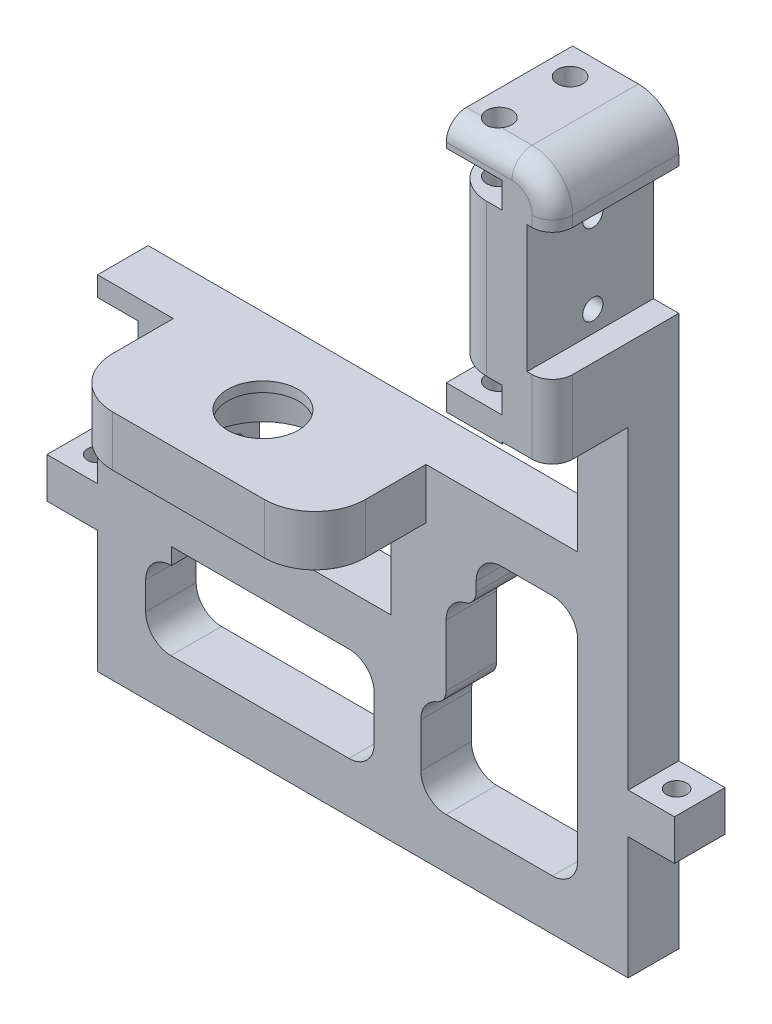
SolidWorks part; units mm, degrees
material "PLA Black"
ref_plane "Front Plane" through (0, 0, 0) normal (0, 0, 1) x (1, 0, 0)
ref_plane "Top Plane" through (0, 0, 0) normal (0, 1, 0) x (1, 0, 0)
ref_plane "Right Plane" through (0, 0, 0) normal (1, 0, 0) x (0, 0, -1)
sketch "Sketch1" plane through (0, 0, 0) normal (0, 0, 1) x (1, 0, 0)
  line L0 (-68.0673, -53.1516) -> (46.9327, -53.1516)
  line L1 (56.0827, -20.9516) -> (56.0827, -28.9516)
  line L2 (56.0827, -20.9516) -> (46.9327, -20.9516)
  line L3 (46.9327, -20.9516) -> (46.9327, 91.0484)
  line L4 (46.9327, 91.0484) -> (36.6057, 91.0484)
  line L5 (36.9327, 86.0484) -> (36.9327, 80.9484)
  line L6 (36.9327, 25.6935) -> (36.9327, 22.1505)
  line L7 (36.9327, 22.1505) -> (36.9327, 14.8484)
  line L8 (36.9327, 14.8484) -> (-58.0673, 14.8484)
  line L9 (-58.0673, 14.8484) -> (-58.0673, -20.9516)
  line L10 (-58.0673, -20.9516) -> (-68.0673, -20.9516)
  line L11 (-68.0673, -20.9516) -> (-68.0673, -53.1516)
  line L12 (56.0827, -28.9516) -> (46.9327, -28.9516)
  line L13 (46.9327, -28.9516) -> (46.9327, -53.1516)
  line L14 (36.9327, 50.9484) -> (36.9327, 45.8484)
  line L15 (36.6057, 91.0484) -> (25.9327, 91.0484)
  line L16 (36.9327, 80.9484) -> (25.9327, 80.9484)
  line L17 (36.9327, 86.0484) -> (25.9327, 86.0484)
  line L18 (25.9327, 91.0484) -> (25.9327, 86.0484)
  line L19 (36.9327, 40.8484) -> (36.9327, 25.6935)
  line L20 (36.9327, 50.9484) -> (25.9327, 50.9484)
  line L21 (25.9327, 80.9484) -> (25.9327, 50.9484)
  line L22 (36.9327, 45.8484) -> (25.9327, 45.8484)
  line L24 (36.9327, 40.8484) -> (25.9327, 40.8484)
  line L25 (25.9327, 45.8484) -> (25.9327, 40.8484)
  dimension "D1" = 30
  dimension "D2" = 5.1
  dimension "D3" = 5.1
  dimension "D4" = 11
  dimension "D5" = 21
  dimension "D6" = 115
  dimension "D7" = 10
  dimension "D8" = 8
  dimension "D9" = 24.2
  dimension "D10" = 26
  dimension "D11" = 5
  dimension "D12" = 5
  dimension "D13" = 112
extrude "Extrude1" add sketch "Sketch1" along normal blind 10
sketch "Sketch2" plane through (0, 0, 10) normal (0, 0, 1) x (1, 0, 0)
  line L0 (25.9327, 91.0484) -> (46.9327, 91.0484)
  line L1 (46.9327, 91.0484) -> (46.9327, 41.2275)
  line L2 (46.9327, -20.9516) -> (46.9327, 91.0484) construction
  line L3 (46.9327, 41.2275) -> (36.9327, 41.2275)
  line L4 (36.9327, 86.0484) -> (36.9327, 80.9484) construction
  line L5 (36.9327, 41.2275) -> (36.9327, 40.8484)
  line L6 (36.9327, 86.0484) -> (25.9327, 86.0484)
  line L7 (25.9327, 86.0484) -> (25.9327, 91.0484)
  line L8 (36.9327, 80.9484) -> (36.9327, 86.0484)
  line L9 (25.9327, 80.9484) -> (36.9327, 80.9484)
  line L10 (25.9327, 80.9484) -> (25.9327, 50.9484)
  line L11 (25.9327, 50.9484) -> (36.9327, 50.9484)
  line L12 (36.9327, 45.8484) -> (36.9327, 50.9484)
  line L13 (25.9327, 45.8484) -> (36.9327, 45.8484)
  line L14 (25.9327, 45.8484) -> (25.9327, 40.8484)
  line L15 (25.9327, 40.8484) -> (36.9327, 40.8484)
extrude "Extrude2" add sketch "Sketch2" along normal blind 15
fillet "Fillet1" radius 8 2 edges at (25.9327, 65.9484, 0) (25.9327, 65.9484, 25)
sketch "Sketch3" plane through (0, 91.0484, 0) normal (0, 1, 0) x (-1, 0, 0)
  line L0 (-46.9327, 0) -> (-25.9327, 0) construction
  line L1 (-30.9327, 0) -> (-30.9327, 25) construction
  line L2 (-46.9327, 25) -> (-25.9327, 25) construction
  line L3 (-25.9327, 25) -> (-25.9327, 0) construction
  circle A0 centre (-30.9327, 5.5) radius 2.5
  circle A1 centre (-30.9327, 19.5) radius 2.5
  dimension "D2" = 5
  dimension "D1" = 14
  dimension "D3" = 5.5
  dimension "D4" = 5
extrude "Cut-Extrude1" cut sketch "Sketch3" against normal blind 53.683
fillet "Fillet4" radius 8 1 edges at (46.9327, 91.0484, 12.5)
fillet "Fillet7" radius 4 3 edges at (46.9327, 62.1379, 25) (32.4327, 91.0484, 25) (44.5895, 88.7052, 25)
sketch "Sketch4" plane through (0, 0, 0) normal (0, 0, -1) x (-1, 0, 0)
  line L0 (-46.9327, -20.9516) -> (-46.9327, 83.0484) construction
  line L1 (-46.9327, 80.9484) -> (-41.9327, 80.9484)
  line L2 (-46.9327, 80.9484) -> (-46.9327, 55.7484)
  line L3 (-46.9327, 55.7484) -> (-41.9327, 55.7484)
  line L4 (-41.9327, 80.9484) -> (-41.9327, 55.7484)
  line L5 (-36.9327, 80.9484) -> (-33.9327, 80.9484) construction
  dimension "D1" = 5
  dimension "D2" = 25.2
extrude "Extrude3" cut sketch "Sketch4" against normal through all
hole_wizard "Ø4.0 (4) Diameter Hole1" positions "3DSketch1" profile "Sketch5" hole size "Ø4.0" standard "Ansi Metric"
sketch3d "3DSketch1"
  line L0 (41.9327, 55.7484, 12) -> (41.9327, 80.9484, 12) construction
  line L1 (41.9327, 55.7484, 25) -> (41.9327, 55.7484, 0) construction
  line L2 (41.9327, 80.9484, 25) -> (41.9327, 80.9484, 0) construction
  line L5 (41.9327, 55.7484, 0) -> (41.9327, 80.9484, 0) construction
  point P0 (41.9327, 75.9484, 12)
  point P2 (41.9327, 59.9484, 12)
  dimension "D1" = 12
  dimension "D2" = 16
  dimension "D3" = 5
sketch "Sketch5" plane through (41.9327, 75.9484, 12) normal (0, 1, 0) x (0, 0, -1)
  line L0 (0, 0) -> (0, 15)
  line L1 (0, 15) -> (2, 15)
  line L2 (2, 15) -> (2, 0)
  line L5 (2, 0) -> (0, 0)
  line L10 (0, 15) -> (-2, 15) construction
  line L11 (0, -6.35) -> (0, 107.95) construction
  dimension "Hole Dia." = 4
  dimension "Hole Depth" = 15
  dimension "Drill Angle" = 180
sketch "Sketch6" plane through (0, 0, 10) normal (0, 0, 1) x (1, 0, 0)
  line L0 (36.9327, 14.8484) -> (-58.0673, 14.8484) construction
  line L1 (6.9327, 14.8484) -> (-43.0673, 14.8484)
  line L2 (6.9327, 14.8484) -> (6.9327, 4.8484)
  line L3 (6.9327, 4.8484) -> (-43.0673, 4.8484)
  line L4 (-43.0673, 14.8484) -> (-43.0673, 4.8484)
  line L5 (46.9327, -20.9516) -> (46.9327, 41.2275) construction
  dimension "D1" = 10
  dimension "D2" = 50
  dimension "D3" = 40
extrude "Extrude4" add sketch "Sketch6" along normal blind 22
sketch "Sketch7" plane through (0, 0, 10) normal (0, 0, 1) x (1, 0, 0)
  line L0 (-43.0673, 4.8484) -> (6.9327, 4.8484) construction
  line L1 (0, 4.8484) -> (-35.9916, 4.8484)
  line L2 (0, 4.8484) -> (0, -14.4098)
  line L3 (0, -14.4098) -> (-35.9916, -14.4098)
  line L4 (-35.9916, 4.8484) -> (-35.9916, -14.4098)
extrude "Extrude5" cut sketch "Sketch7" against normal blind 65
sketch "Sketch8" plane through (0, 4.8484, 0) normal (0, -1, 0) x (1, 0, 0)
  circle A0 centre (-18.5673, 16.7712) radius 7
  circle A1 centre (-18.5673, 16.7712) radius 8 construction
  dimension "D1" = 14
extrude "Extrude6" cut sketch "Sketch8" against normal blind 65
sketch "Sketch9" plane through (0, 4.8484, 0) normal (0, -1, 0) x (1, 0, 0)
  circle A0 centre (-18.5673, 16.7712) radius 11.25
  dimension "D1" = 22.5
extrude "Extrude7" cut sketch "Sketch9" against normal blind 8
sketch "Sketch10" plane through (0, 0, 10) normal (0, 0, 1) x (1, 0, 0)
  line L2 (-68.0673, -53.1516) -> (46.9327, -53.1516) construction
  line L3 (36.9327, 4.8484) -> (16.849, 4.8484)
  line L4 (36.9327, 4.8484) -> (36.9327, -43.1516)
  line L5 (36.9327, -43.1516) -> (16.849, -43.1516)
  line L6 (16.849, 4.8484) -> (16.849, -4.8134)
  line L7 (16.849, -4.8134) -> (10.8978, -4.8134)
  line L8 (46.9327, -20.9516) -> (46.9327, 41.2275) construction
  line L9 (16.849, -43.1516) -> (10.8978, -43.1516)
  line L10 (10.8978, -4.8134) -> (10.8978, -24.4098)
  line L11 (10.8978, -43.1516) -> (5.8917, -43.1516)
  line L12 (-35.9916, -14.4098) -> (0, -14.4098) construction
  line L13 (10.8978, -24.4098) -> (5.8917, -24.4098)
  line L14 (36.9327, 14.8484) -> (6.9327, 14.8484) construction
  line L15 (-43.4499, -27.6686) -> (-48.5527, -27.6686)
  line L16 (-43.4499, -27.6686) -> (-43.4499, -24.4098)
  line L17 (-45.604, -43.1516) -> (-48.5527, -43.1516)
  line L18 (-48.5527, -27.6686) -> (-48.5527, -43.1516)
  line L19 (5.8917, -24.4098) -> (5.8917, -43.1516)
  line L20 (-3.3285, -24.4098) -> (-3.3285, -43.1516)
  line L21 (-3.3285, -24.4098) -> (-43.4499, -24.4098)
  line L22 (-3.3285, -43.1516) -> (-45.604, -43.1516)
  dimension "D1" = 10
  dimension "D2" = 10
  dimension "D3" = 10
  dimension "D4" = 10
fillet "Fillet8" radius 10 2 edges at (6.9327, 9.8484, 32) (-43.0673, 9.8484, 32)
sketch "Sketch11" plane through (0, 0, 10) normal (0, 0, 1) x (1, 0, 0)
  line L0 (-58.0673, -20.9516) -> (-68.0673, -20.9516) construction
  line L1 (-68.0673, -53.1516) -> (-58.0673, -53.1516)
  line L2 (-68.0673, -53.1516) -> (-68.0673, -28.9516)
  line L3 (-68.0673, -28.9516) -> (-58.0673, -28.9516)
  line L4 (-58.0673, -53.1516) -> (-58.0673, -28.9516)
  line L5 (-58.0673, 14.8484) -> (-58.0673, -20.9516) construction
  dimension "D1" = 8
extrude "Extrude9" cut sketch "Sketch11" against normal blind 28
hole_wizard "Ø4.0 (4) Diameter Hole2" positions "3DSketch2" profile "Sketch12" hole size "Ø4.0" standard "Ansi Metric"
sketch3d "3DSketch2"
  line L0 (56.0827, -20.9516, 10) -> (46.9327, -20.9516, 10) construction
  line L1 (56.0827, -20.9516, 10) -> (56.0827, -20.9516, 0) construction
  line L2 (-58.0673, -20.9516, 10) -> (-68.0673, -20.9516, 10) construction
  line L3 (-68.0673, -20.9516, 10) -> (-68.0673, -20.9516, 0) construction
  point P1 (-63.0673, -20.9516, 5)
  point P3 (51.5077, -20.9516, 5)
  point P8 (51.5077, -20.9516, 10)
  point P11 (56.0827, -20.9516, 5)
  point P14 (-63.0673, -20.9516, 10)
  point P17 (-68.0673, -20.9516, 5)
sketch "Sketch12" plane through (-63.0673, -20.9516, 5) normal (1, 0, 0) x (0, 0, 1)
  line L0 (0, 0) -> (0, 15)
  line L1 (0, 15) -> (2, 15)
  line L2 (2, 15) -> (2, 0)
  line L5 (2, 0) -> (0, 0)
  line L10 (0, 15) -> (-2, 15) construction
  line L11 (0, -6.35) -> (0, 107.95) construction
  dimension "Hole Dia." = 4
  dimension "Hole Depth" = 15
  dimension "Drill Angle" = 180
sketch "Sketch13" plane through (0, 0, 10) normal (0, 0, 1) x (1, 0, 0)
  line L0 (-58.0673, 14.8484) -> (-58.0673, -20.9516) construction
  line L1 (-58.0673, 10.9504) -> (-50.0673, 10.9504)
  line L2 (-58.0673, 10.9504) -> (-58.0673, -11.0496)
  line L3 (-58.0673, -11.0496) -> (-50.0673, -11.0496)
  line L4 (-50.0673, 10.9504) -> (-50.0673, -11.0496)
  dimension "D1" = 8
  dimension "D2" = 22
extrude "Cut-Extrude2" cut sketch "Sketch13" against normal blind 16
hole_wizard "Ø4.0 (4) Diameter Hole3" positions "3DSketch3" profile "Sketch14" hole size "Ø4.0" standard "Ansi Metric"
sketch3d "3DSketch3"
  line L0 (-50.0673, -11.0496, 10) -> (-50.0673, 10.9504, 10) construction
  line L1 (-50.0673, 10.9504, 0) -> (-50.0673, 10.9504, 10) construction
  point P0 (-50.0673, 5.9504, 5)
  point P2 (-50.0673, -6.0496, 5)
  dimension "D1" = 12
  dimension "D2" = 5
  dimension "D3" = 5
sketch "Sketch14" plane through (-50.0673, 5.9504, 5) normal (0, 1, 0) x (0, 0, 1)
  line L0 (0, 0) -> (0, 15)
  line L1 (0, 15) -> (1.95, 15)
  line L2 (1.95, 15) -> (1.95, 0)
  line L5 (1.95, 0) -> (0, 0)
  line L10 (0, 15) -> (-1.95, 15) construction
  line L11 (0, -6.35) -> (0, 107.95) construction
  dimension "Hole Dia." = 3.9
  dimension "Hole Depth" = 15
  dimension "Drill Angle" = 180
extrude "Extrude10" cut sketch "Sketch10" against normal blind 10
fillet "Fillet9" radius 5 10 edges at (-48.5527, -43.1516, 5) (-48.5527, -27.6686, 5) (-3.3285, -24.4098, 5) (-3.3285, -43.1516, 5) (36.9327, -43.1516, 5) (5.8917, -43.1516, 5) (10.8978, -4.8134, 5) (5.8917, -24.4098, 5) (16.849, 4.8484, 5) (36.9327, 4.8484, 5)
fillet "Fillet10" radius 3 3 edges at (-43.4499, -26.0392, 0) (16.849, -4.8134, 5) (10.8978, -24.4098, 5)
